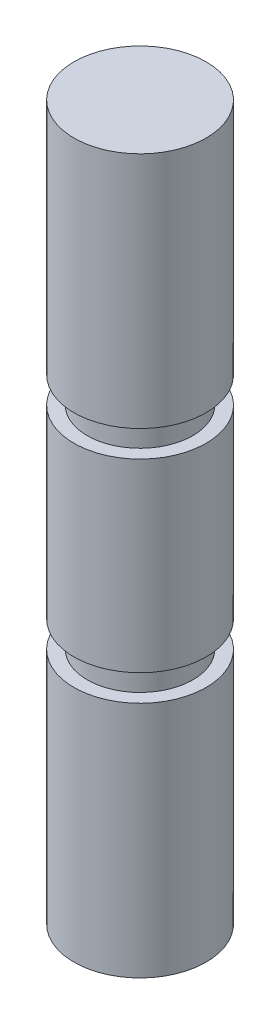
SolidWorks part; units mm, degrees
material "普通碳钢"
ref_plane "前视基准面" through (0, 0, 0) normal (0, 0, 1) x (1, 0, 0)
ref_plane "上视基准面" through (0, 0, 0) normal (0, 1, 0) x (1, 0, 0)
ref_plane "右视基准面" through (0, 0, 0) normal (1, 0, 0) x (0, 0, -1)
sketch "草图1" plane through (0, 0, 0) normal (1, 0, 0) x (0, 0, -1)
  line L0 (0, -13.5) -> (0, 21.2269) construction
  line L1 (0, 13.5) -> (2.5, 13.5)
  line L2 (2.5, 13.5) -> (2.5, 4.5)
  line L3 (2.5, 4.5) -> (2, 4.5)
  line L4 (2.5, 3.5) -> (2.5, -3.5)
  line L5 (2.5, -3.5) -> (2, -3.5)
  line L6 (2, -3.5) -> (2, -4.5)
  line L7 (2, -4.5) -> (2.5, -4.5)
  line L8 (2.5, -4.5) -> (2.5, -13.5)
  line L9 (2.5, -13.5) -> (0, -13.5)
  line L10 (0, -13.5) -> (0, 13.5)
  line L11 (2, 4.5) -> (2, 3.5)
  line L12 (2, 3.5) -> (2.5, 3.5)
  dimension "D1" = 2.5
  dimension "D2" = 7
  dimension "D3" = 1
  dimension "D4" = 1
  dimension "D5" = 0.5
  dimension "D6" = 9
  dimension "D7" = 9
revolve "旋转1" add sketch "草图1" angle 360 about L0
